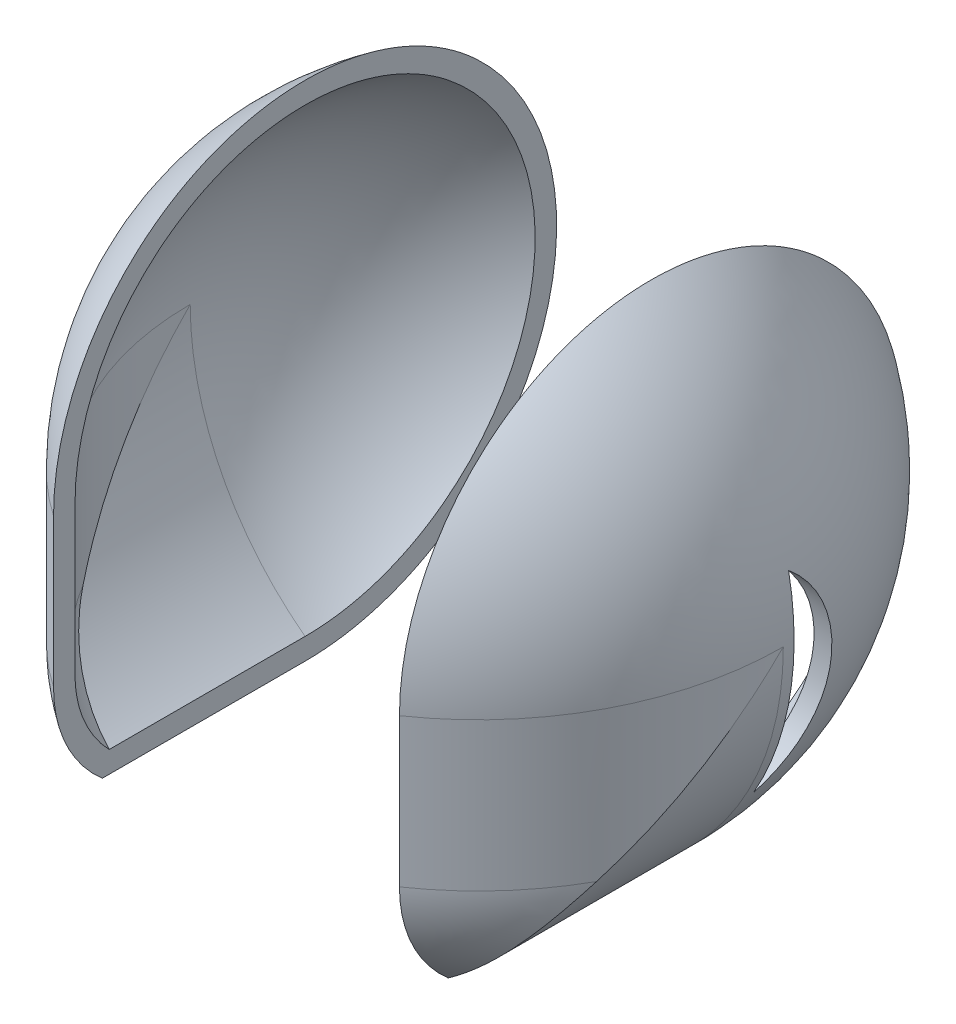
SolidWorks part; units mm, degrees
ref_plane "Alzado" through (0, 0, 0) normal (0, 0, 1) x (1, 0, 0)
ref_plane "Planta" through (0, 0, 0) normal (0, 1, 0) x (1, 0, 0)
ref_plane "Vista lateral" through (0, 0, 0) normal (1, 0, 0) x (0, 0, -1)
sketch "Croquis1" plane through (0, 0, 0) normal (0, 0, 1) x (1, 0, 0)
  line L0 (0, 35) -> (0, -35)
  arc A0 (0, 35) -> (0, -35) centre (0, 0) ccw
revolve "Revolución1" add sketch "Croquis1" angle 360 about L0
sketch "Croquis3" plane through (0, 0, 0) normal (0, 0, 1) x (1, 0, 0)
  line L0 (0, 16.9366) -> (0, 6.4344)
  line L1 (0, 0) -> (35, 0)
  line L2 (0, 0) -> (0, -35)
  line L3 (0, -35) -> (17, -35)
  line L4 (35, 0) -> (35, -17)
  arc A0 (35, -17) -> (17, -35) centre (17, -17) cw
  dimension "D1" = 18
revolve "Revolución18" add sketch "Croquis3" angle 180 about L2 region at (16.6889, -16.6889, 0)
sketch "Croquis4" plane through (0, 0, 0) normal (0, 0, 1) x (1, 0, 0)
  circle A0 centre (0, 0) radius 42.0416
  circle A1 centre (0, 0) radius 35
extrude "Cortar-Extruir1" cut sketch "Croquis4" along normal blind 53
sketch "Croquis5" plane through (0, 0, 0) normal (0, 0, 1) x (1, 0, 0)
  line L2 (-22, 31.1367) -> (-19.83, 31.1367)
  line L4 (-22, 31.1367) -> (-36.6096, 31.1367)
  line L6 (-22, -33.3554) -> (-36.6096, -33.3554)
  line L7 (-36.6096, 31.1367) -> (-36.6096, -33.3554)
  line L8 (22, 31.1367) -> (35, 31.1367)
  line L9 (-22, -33.3554) -> (-19.83, -33.3554)
  line L10 (22, -36.1659) -> (35, -36.1659)
  line L11 (35, 31.1367) -> (35, -36.1659)
  line L12 (22, -36.1659) -> (-19.83, -36.1659)
  line L13 (22, 31.1367) -> (19.83, 31.1367)
  line L14 (19.83, 36.6364) -> (-19.83, 36.6364)
  line L18 (-19.83, 36.6364) -> (19.83, 36.6364)
  line L19 (-19.83, 36.6364) -> (-19.83, -36.1659)
  line L20 (-19.83, -36.1659) -> (19.83, -36.1659)
  line L21 (19.83, 36.6364) -> (19.83, -36.1659)
sketch "Croquis6" plane through (0, 0, 0) normal (0, 0, 1) x (1, 0, 0)
  line L0 (-34.7269, -4.3636) -> (-16.7269, -4.3636)
  line L1 (34.7543, -4.1399) -> (16.7543, -4.1399)
  arc A0 (-35, 0) -> (-30.5941, -17) centre (0, 0) ccw construction
  arc A1 (30.5941, -17) -> (35, 0) centre (0, 0) ccw construction
  ellipse E0 centre (-16.7269, -4.3636) end of major axis (-16.7269, 9.6364) minor radius 11
  ellipse E1 centre (16.7543, -4.1399) end of major axis (16.7543, -18.1399) minor radius 11
extrude "Cortar-Extruir4" cut sketch "Croquis5" against normal blind 38 and the other way blind 38 contours L12 L14 region at (0, 0.2353, 0)
shell "Vaciado3" thickness 2 removed face at (-19.83, -6.0348, -1.2905)
shell "Vaciado4" thickness 2 removed face at (19.83, -6.0348, -1.2905)
sketch "Croquis8" plane through (25.3401, 3.698, -6.7717) normal (1, 0, 0) x (0, 0, -1)
  line L0 (-35.6121, -20.698) -> (-35.6121, -3.698) construction
  line L1 (-45.1701, -32.5384) -> (-45.1701, 25.1425) construction
  line L2 (-45.1701, 3.2226) -> (-45.1701, -20.1089)
  spline S0 degree 3 poles (-45.1701, -20.1089) (-47.2647, -18.2737) (-49.3582, -14.2824) (-50.3574, -5.6838) (-48.3923, 0.2217) (-45.1701, 3.2226) knots 0 0 0 0 0.319266 0.506234 1 1 1 1
  spline S1 degree 3 number of poles 824 (-39.1107, 5.5964) -> (-39.3361, -22.4027) construction
extrude "Cortar-Extruir5" cut sketch "Croquis8" along normal blind 44 rebuild error yes
sketch "Croquis11" plane through (25.3401, 3.698, -6.7717) normal (1, 0, 0) x (0, 0, -1)
  line L0 (-5.5101, -20.698) -> (-5.5101, -32.5384) construction
  line L1 (-5.5101, 22.6795) -> (-5.5101, -30.0755) construction
  line L2 (-5.5101, 25.1425) -> (-5.5101, -32.5384) construction
  line L3 (-5.5101, 2.9287) -> (-5.5101, -21.0897)
  spline S0 degree 3 poles (-5.5101, -21.0897) (-3.3802, -19.4432) (-0.7928, -15.11) (0.2265, -6.054) (-2.2355, 0.2688) (-5.5101, 2.9287) knots 0 0 0 0 0.29719 0.54021 1 1 1 1
  spline S1 degree 3 number of poles 825 (-10.9681, -23.0287) -> (-11.1865, 4.97) construction
extrude "Cortar-Extruir11" cut sketch "Croquis11" along normal blind 50
